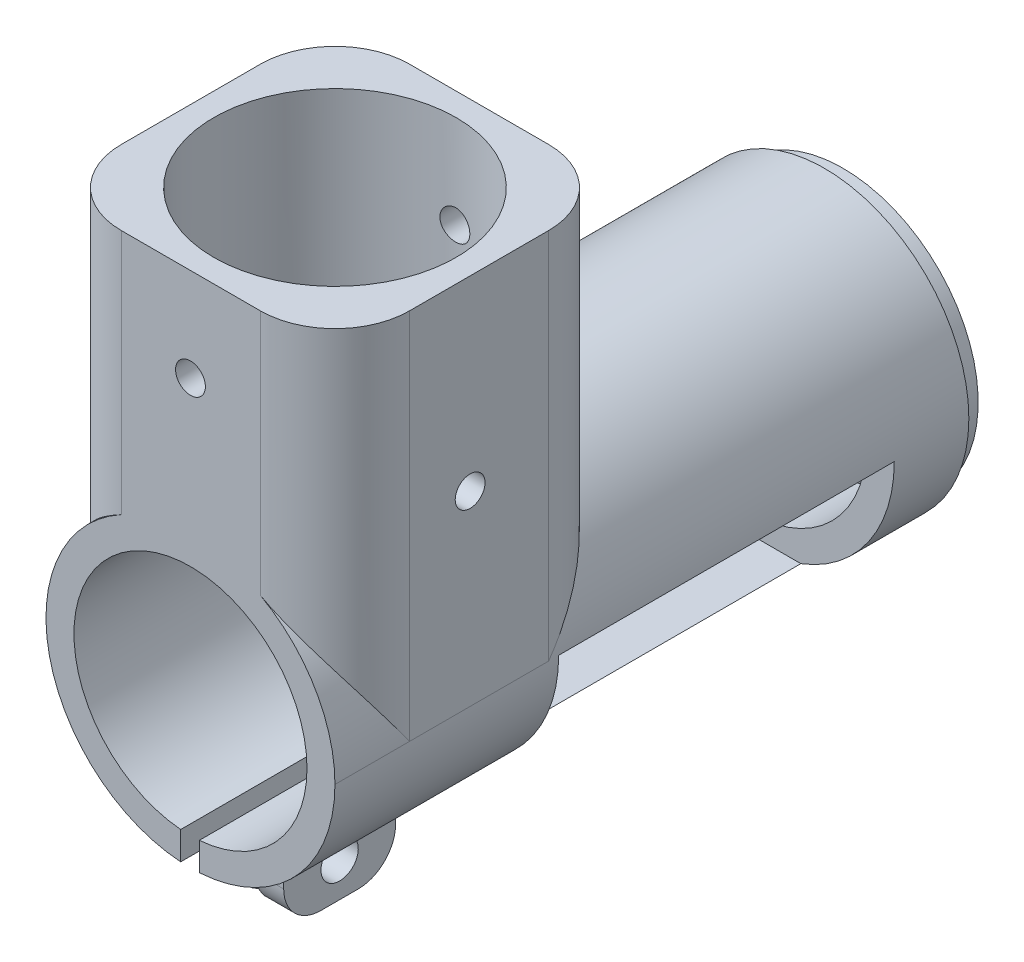
SolidWorks part; units mm, degrees
ref_plane "Front" through (0, 0, 0) normal (0, 0, 1) x (1, 0, 0)
ref_plane "Top" through (0, 0, 0) normal (0, 1, 0) x (1, 0, 0)
ref_plane "Right" through (0, 0, 0) normal (1, 0, 0) x (0, 0, -1)
sketch "Эскиз1" plane through (0, 0, 0) normal (0, 0, 1) x (1, 0, 0)
  circle A0 centre (0, 0) radius 12.5
  circle A1 centre (0, 0) radius 15.5
extrude "Бобышка-Вытянуть1" add sketch "Эскиз1" along normal blind 68
sketch "Эскиз2" plane through (0, 0, 0) normal (0, 0, -1) x (-1, 0, 0)
  circle A0 centre (0, 0) radius 14.5
  circle A2 centre (8.5, 0) radius 1.6
  circle A3 centre (-8.5, 0) radius 1.6
  circle A4 centre (0, 0) radius 5
extrude "Бобышка-Вытянуть2" add sketch "Эскиз2" along normal blind 2
sketch "Эскиз3" plane through (0, 0, 0) normal (0, 1, 0) x (1, 0, 0)
  line L2 (-7.4174, -37.0826) -> (7.5, -37.0826)
  line L3 (-15.4174, -45.0826) -> (-15.4174, -60)
  line L4 (-7.4174, -68) -> (7.5, -68)
  line L5 (15.5, -45.0826) -> (15.5, -60)
  line L6 (-15.4174, -37.0826) -> (15.5, -68) construction
  line L7 (-15.4174, -68) -> (15.5, -37.0826) construction
  circle A3 centre (0.0413, -52.5413) radius 13
  arc A4 (-15.4174, -60) -> (-7.4174, -68) centre (-7.4174, -60) ccw
  arc A5 (7.5, -68) -> (15.5, -60) centre (7.5, -60) ccw
  arc A6 (7.5, -37.0826) -> (15.5, -45.0826) centre (7.5, -45.0826) cw
  arc A7 (-7.4174, -37.0826) -> (-15.4174, -45.0826) centre (-7.4174, -45.0826) ccw
  dimension "D1" = 8
extrude "Бобышка-Вытянуть3" add sketch "Эскиз3" along normal blind 40
sketch "Эскиз4" plane through (0, 0, 68) normal (0, 0, 1) x (1, 0, 0)
  circle A0 centre (0, 0) radius 12.5
extrude "Вырез-Вытянуть1" cut sketch "Эскиз4" against normal blind 40
sketch "Эскиз5" plane through (0, 0, 0) normal (0, 0, 1) x (1, 0, 0)
  circle A1 centre (0, 30) radius 1.6
extrude "Вырез-Вытянуть4" cut sketch "Эскиз5" along normal through all
sketch "Эскиз6" plane through (0, 0, 0) normal (1, 0, 0) x (0, 0, -1)
  circle A1 centre (-53.5, 20) radius 1.6
extrude "Вырез-Вытянуть5" cut sketch "Эскиз6" against normal blind 40 and the other way blind 40
sketch "Эскиз7" plane through (0, 0, 0) normal (1, 0, 0) x (0, 0, -1)
  line L1 (-8, -14.5) -> (-44, -14.5)
  line L2 (-8, -14.5) -> (-8, 0)
  line L3 (-8, 0) -> (-44, 0)
  line L4 (-44, -14.5) -> (-44, 0)
extrude "Вырез-Вытянуть6" cut sketch "Эскиз7" against normal through all and the other way through all
sketch "Эскиз8" plane through (0, 0, 68) normal (0, 0, 1) x (1, 0, 0)
  line L1 (-1.0471, -10.2054) -> (0.9529, -10.2054)
  line L2 (-1.0471, -10.2054) -> (-1.0471, -20.7945)
  line L3 (-1.0471, -20.7945) -> (0.9529, -20.7945)
  line L4 (0.9529, -10.2054) -> (0.9529, -20.7945)
  line L5 (-1.0471, -10.2054) -> (0.9529, -20.7945) construction
  line L6 (-1.0471, -20.7945) -> (0.9529, -10.2054) construction
  arc A0 (-7.4174, 13.61) -> (7.5, 13.5647) centre (0, 0) ccw construction
  point P0 (-0.0471, -15.4999)
extrude "Вырез-Вытянуть7" cut sketch "Эскиз8" against normal blind 40
ref_plane "Плоскость1" through (0, 0, 56) normal (0, 0, -1) x (-1, 0, 0)
sketch "Эскиз9" plane through (0, 0, 56) normal (0, 0, -1) x (-1, 0, 0)
  line L5 (1.0471, -12.4561) -> (5, -12.4561)
  line L6 (1.0471, -12.4561) -> (1.0471, -22.4599)
  line L7 (1.0471, -22.4599) -> (5, -22.4599)
  line L8 (5, -12.4561) -> (5, -22.4599)
  line L9 (-0.9529, -12.4636) -> (-4, -12.4636)
  line L10 (-0.9529, -12.4636) -> (-0.9529, -22.4599)
  line L11 (-0.9529, -22.4599) -> (-4, -22.4599)
  line L12 (-4, -12.4636) -> (-4, -22.4599)
extrude "Бобышка-Вытянуть4" add sketch "Эскиз9" along normal blind 6 and the other way blind 6
sketch "Эскиз10" plane through (4, 0, 0) normal (1, 0, 0) x (0, 0, -1)
  line L0 (-62, -14.975) -> (-50, -22.4599) construction
  circle A0 centre (-56, -18.7175) radius 2
extrude "Вырез-Вытянуть8" cut sketch "Эскиз10" against normal through all
sketch "Эскиз11" plane through (-5, 0, 0) normal (-1, 0, 0) x (0, 0, 1)
  line L1 (60.0415, -18.7175) -> (58.0207, -15.2175)
  line L2 (58.0207, -15.2175) -> (53.9793, -15.2175)
  line L3 (53.9793, -15.2175) -> (51.9585, -18.7175)
  line L4 (51.9585, -18.7175) -> (53.9793, -22.2175)
  line L5 (53.9793, -22.2175) -> (58.0207, -22.2175)
  line L6 (58.0207, -22.2175) -> (60.0415, -18.7175)
  circle A0 centre (56, -18.7175) radius 3.5 construction
extrude "Вырез-Вытянуть9" cut sketch "Эскиз11" against normal blind 2
fillet "Скругление1" radius 4 4 edges at (-3.0235, -22.4599, 50) (-3.0235, -22.4599, 62) (2.4765, -22.4599, 62) (2.4765, -22.4599, 50)
sketch "Эскиз12" plane through (0, 40, 0) normal (0, 1, 0) x (1, 0, 0)
  line L0 (0.0413, -65.5413) -> (0.0413, -68) construction
  line L1 (-7.4174, -68) -> (7.5, -68) construction
  circle A0 centre (0.0413, -52.5413) radius 13 construction
  point P6 (0, 0)
